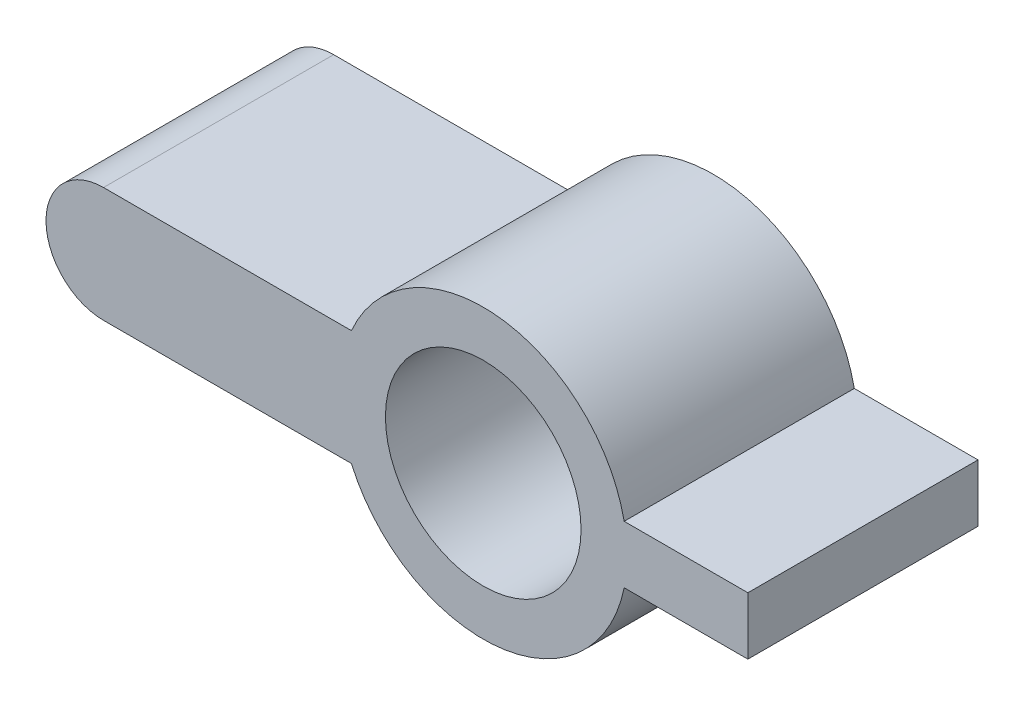
SolidWorks part; units mm, degrees
ref_plane "Front Plane" through (0, 0, 0) normal (0, 0, 1) x (1, 0, 0)
ref_plane "Top Plane" through (0, 0, 0) normal (0, 1, 0) x (1, 0, 0)
ref_plane "Right Plane" through (0, 0, 0) normal (1, 0, 0) x (0, 0, -1)
sketch "Sketch1" plane through (0, 0, 0) normal (0, 1, 0) x (1, 0, 0)
  line L1 (-1.15, 1) -> (0, 1)
  line L2 (-1.15, 1) -> (-1.15, 0)
  line L3 (-1.15, 0) -> (0, 0)
  line L4 (0, 1) -> (0, 0)
  dimension "D1" = 1.15
  dimension "D2" = 1
extrude "Boss-Extrude1" add sketch "Sketch1" along normal blind 0.25
sketch "Sketch2" plane through (-1.15, 0, 0) normal (-1, 0, 0) x (0, 0, 1)
  line L0 (-1, 0.25) -> (-1, 0) construction
  line L2 (-1, 0.25) -> (0, 0.25) construction
  line L3 (0, -0.125) -> (-1, -0.125)
  line L4 (0, -0.125) -> (0, 0.375)
  line L5 (0, 0.375) -> (-1, 0.375)
  line L6 (-1, -0.125) -> (-1, 0.375)
  point P3 (-0.5, 0.25)
  point P4 (-0.5, -0.125)
  point P7 (-1, 0.125)
  point P8 (-1, 0.125)
  point P12 (0, 0)
  point P14 (0, 0)
  dimension "D2" = 0.5
  dimension "D3" = 1
extrude "Boss-Extrude2" add sketch "Sketch2" along normal blind 1.9 contours L4 L3 L6 L5
sketch "Sketch3" plane through (0, 0, -1) normal (0, 0, -1) x (-1, 0, 0)
  line L1 (0, 0.25) -> (0, 0) construction
  circle A0 centre (1.15, 0.125) radius 0.625
  point P3 (0, 0.125)
  dimension "D1" = 1.25
  dimension "D2" = 1.15
extrude "Boss-Extrude3" add sketch "Sketch3" against normal blind 1
sketch "Sketch4" plane through (0, 0, 0) normal (0, 0, 1) x (1, 0, 0)
  circle A0 centre (-1.15, 0.125) radius 0.425
  circle A1 centre (-1.15, 0.125) radius 0.625 construction
  dimension "D1" = 0.85
extrude "Cut-Extrude1" cut sketch "Sketch4" against normal through all both contours A0
fillet "Fillet2" radius 0.25 1 edges at (-3.05, 0.375, -0.5)
fillet "Fillet3" radius 0.25 1 edges at (-3.05, -0.125, -0.5)
sketch "Sketch5" plane through (0, 0, 0) normal (0, -1, 0) x (-1, 0, 0)
  line L0 (0, 0) -> (0, 1) construction
  line L1 (0.5, 0.75) -> (0, 0.75)
  line L2 (0.5, 0.75) -> (0.5, 0.25)
  line L3 (0.5, 0.25) -> (0, 0.25)
  line L4 (0, 0.75) -> (0, 0.25)
  line L5 (0.5376, 0) -> (0.5376, 1) construction
  point P8 (0.5376, 0.5)
  point P9 (0.5, 0.5)
  dimension "D1" = 0.5
  dimension "D2" = 0.5
sketch "Sketch6" plane through (0, 0.25, 0) normal (0, 1, 0) x (1, 0, 0)
  line L0 (0, 0) -> (0, 1) construction
  line L1 (-0.5, 0.25) -> (0, 0.25)
  line L2 (-0.5, 0.25) -> (-0.5, 0.75)
  line L3 (-0.5, 0.75) -> (0, 0.75)
  line L4 (0, 0.25) -> (0, 0.75)
  line L5 (-0.5376, 0) -> (-0.5376, 1) construction
  point P7 (-0.5, 0.5)
  point P9 (-0.5376, 0.5)
  dimension "D1" = 0.5
  dimension "D2" = 0.5
